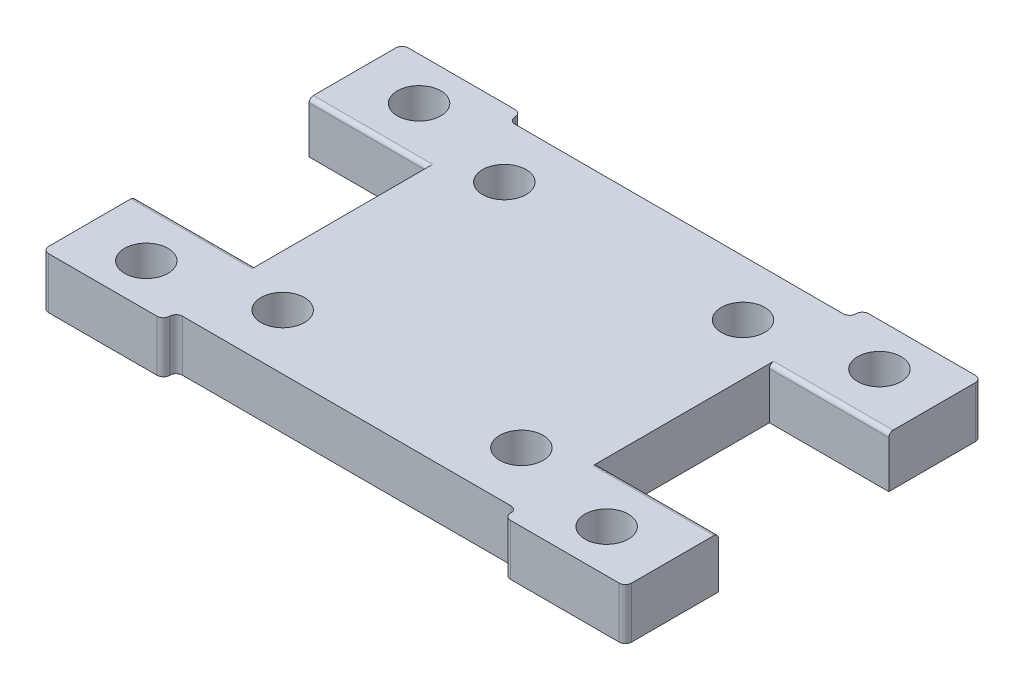
SolidWorks part; units mm, degrees
material "Alloy Steel"
ref_plane "Front Plane" through (0, 0, 0) normal (0, 0, 1) x (1, 0, 0)
ref_plane "Top Plane" through (0, 0, 0) normal (0, 1, 0) x (1, 0, 0)
ref_plane "Right Plane" through (0, 0, 0) normal (1, 0, 0) x (0, 0, -1)
sketch "Sketch1" plane through (0, 0, 0) normal (0, 1, 0) x (1, 0, 0)
  line L0 (20, 19.5) -> (20, -19.5) construction
  line L1 (-19.26, -19.5) -> (19.26, -19.5)
  line L3 (-19.26, 19.5) -> (19.26, 19.5)
  line L5 (20, 20.24) -> (20, 20.26)
  line L7 (20.74, 21) -> (34, 21)
  line L8 (20, 19.5) -> (-20, -19.5) construction
  line L9 (-20, 19.5) -> (20, -19.5) construction
  line L10 (0, 0) -> (0, 19.5) construction
  line L11 (0, 0) -> (-20, 0) construction
  line L13 (34.2, -21) -> (20.74, -21)
  line L14 (20, -20.26) -> (20, -20.24)
  line L16 (20, 10.1) -> (34, 10.1)
  line L18 (34.2, -10.099) -> (20, -10.099)
  line L19 (20, -10.099) -> (20, 10.1)
  line L20 (-20, 19.5) -> (-20, -19.5) construction
  line L21 (-20, -10.099) -> (-20, 10.1)
  line L22 (-34.2, -10.099) -> (-20, -10.099)
  line L24 (-20, 10.1) -> (-34, 10.1)
  line L25 (-20, -20.26) -> (-20, -20.24)
  line L26 (-34.2, -21) -> (-20.74, -21)
  line L28 (-20.74, 21) -> (-34, 21)
  line L29 (-20, 20.24) -> (-20, 20.26)
  line L30 (34, 10.1) -> (34, 21)
  line L31 (34.2, -10.099) -> (34.2, -21)
  line L32 (-34.2, -10.099) -> (-34.2, -21)
  line L33 (-34, 10.1) -> (-34, 21)
  circle A0 centre (-14, 13) radius 2.55
  circle A1 centre (14, 13) radius 2.55
  circle A2 centre (14, -13) radius 2.55
  circle A3 centre (-14, -13) radius 2.55
  circle A4 centre (27, 16) radius 2.55
  circle A5 centre (27, -16) radius 2.55
  circle A6 centre (-27, -16) radius 2.55
  circle A7 centre (-27, 16) radius 2.55
  arc A12 (-20.74, 21) -> (-20, 20.26) centre (-20.74, 20.26) cw
  arc A13 (-20, 20.24) -> (-19.26, 19.5) centre (-19.26, 20.24) ccw
  arc A14 (20, 20.26) -> (20.74, 21) centre (20.74, 20.26) cw
  arc A15 (19.26, 19.5) -> (20, 20.24) centre (19.26, 20.24) ccw
  arc A16 (19.26, -19.5) -> (20, -20.24) centre (19.26, -20.24) cw
  arc A17 (20.74, -21) -> (20, -20.26) centre (20.74, -20.26) cw
  arc A18 (-20, -20.26) -> (-20.74, -21) centre (-20.74, -20.26) cw
  arc A19 (-19.26, -19.5) -> (-20, -20.24) centre (-19.26, -20.24) ccw
  point P0 (0, 0)
  point P1 (27.1, -16)
  point P46 (27, 10.1)
  point P48 (36, 21)
  point P51 (36, -21)
  point P54 (-36, -21)
  point P57 (-36, 21)
  point P60 (-20, 21)
  point P66 (20, 21)
  point P75 (20, -21)
  point P78 (-20, -21)
  dimension "D5" = 5.1
  dimension "D12" = 20.2
  dimension "D9" = 5.1
  dimension "D1" = 1.5
  dimension "D2" = 39
  dimension "D3" = 40
  dimension "D4" = 1.5
  dimension "D6" = 14
  dimension "D7" = 6.5
  dimension "D8" = 16
  dimension "D10" = 16
  dimension "D11" = 14
extrude "Boss-Extrude1" add sketch "Sketch1" along normal blind 6
fillet "Fillet1" radius 0.74 4 edges at (-34, 3, -21) (-34.2, 3, 21) (34.2, 3, 21) (34, 3, -21)
fillet "Fillet2" radius 0.5 4 edges at (-27, 6, -10.1) (-27.1, 6, 10.099) (27, 6, -10.1) (27.1, 6, 10.099)
